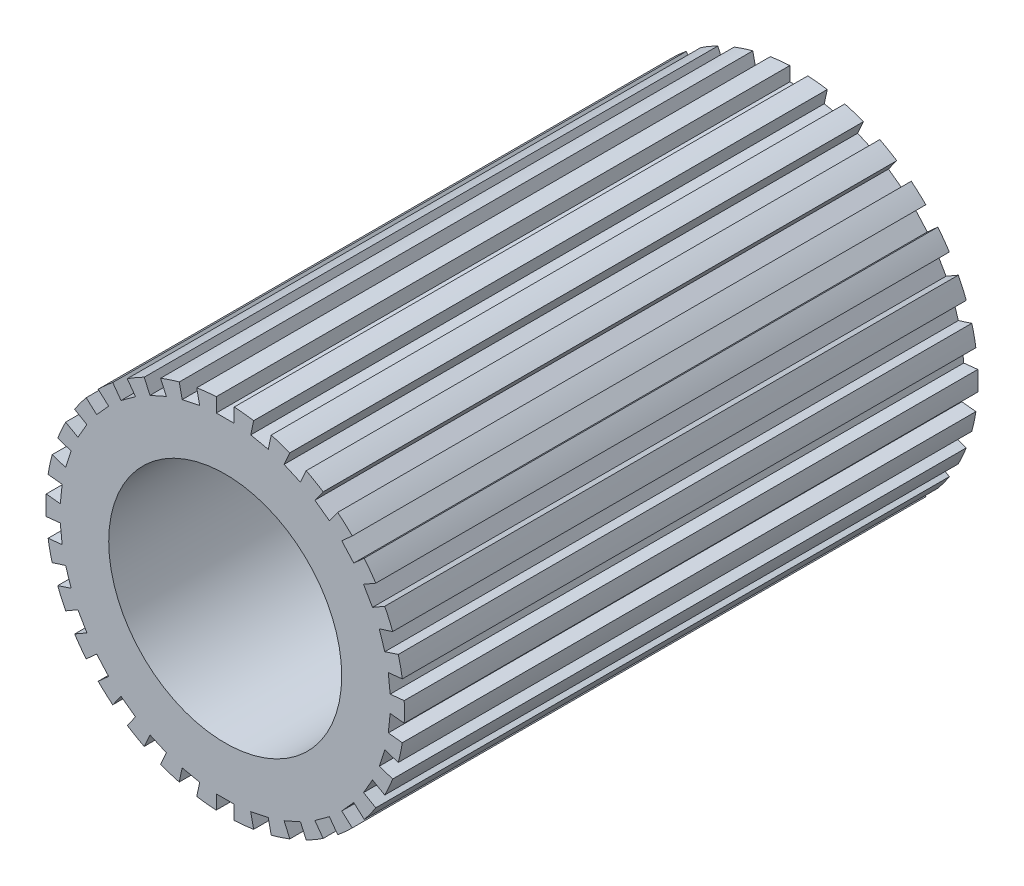
SolidWorks part; units mm, degrees
material "ABS"
ref_plane "Front Plane" through (0, 0, 0) normal (0, 0, 1) x (1, 0, 0)
ref_plane "Top Plane" through (0, 0, 0) normal (0, 1, 0) x (1, 0, 0)
ref_plane "Right Plane" through (0, 0, 0) normal (1, 0, 0) x (0, 0, -1)
sketch "Sketch1" plane through (0, 0, 0) normal (0, 0, 1) x (1, 0, 0)
  circle A0 centre (0, 0) radius 2.5
  circle A1 centre (0, 0) radius 1.625
  dimension "D1" = 3.25
  dimension "D2" = 5
extrude "Boss-Extrude1" add sketch "Sketch1" along normal blind 4
extrude "Boss-Extrude2" add sketch "Sketch1<2>" against normal blind 4 contours A1 | A0 A1 region at (-2.4293, 0, 0) region at (0, 0, 0)
sketch "Sketch1<2>" plane through (0, 0, 0) normal (0, 0, 1) x (1, 0, 0) same geometry as "Sketch1"
sketch "Sketch2" plane through (0, 0, 4) normal (0, 0, 1) x (1, 0, 0)
  line L0 (0.3559, 2.2757) -> (0.5638, 3.2539)
  line L1 (-0.125, 2.3) -> (0.125, 2.3)
  line L2 (-0.125, 2.3) -> (-0.125, 3.3)
  line L3 (-0.125, 3.3) -> (0.125, 3.3)
  line L4 (0.125, 2.3) -> (0.125, 3.3)
  line L5 (0.3559, 2.2757) -> (0.6005, 2.2238)
  line L6 (0.6005, 2.2238) -> (0.8084, 3.2019)
  line L7 (0.5638, 3.2539) -> (0.8084, 3.2019)
  line L8 (0.8213, 2.152) -> (1.228, 3.0655)
  line L9 (0.8213, 2.152) -> (1.0497, 2.0503)
  line L10 (1.0497, 2.0503) -> (1.4564, 2.9639)
  line L11 (1.228, 3.0655) -> (1.4564, 2.9639)
  line L12 (1.2508, 1.9342) -> (1.8386, 2.7432)
  line L13 (1.2508, 1.9342) -> (1.453, 1.7873)
  line L14 (1.453, 1.7873) -> (2.0408, 2.5963)
  line L15 (1.8386, 2.7432) -> (2.0408, 2.5963)
  line L16 (1.6256, 1.6319) -> (2.3687, 2.301)
  line L17 (1.6256, 1.6319) -> (1.7929, 1.4461)
  line L18 (1.7929, 1.4461) -> (2.536, 2.1152)
  line L19 (2.3687, 2.301) -> (2.536, 2.1152)
  line L20 (1.9294, 1.2583) -> (2.7954, 1.7583)
  line L21 (1.9294, 1.2583) -> (2.0544, 1.0417)
  line L22 (2.0544, 1.0417) -> (2.9204, 1.5417)
  line L23 (2.7954, 1.7583) -> (2.9204, 1.5417)
  line L24 (2.1488, 0.8296) -> (3.0999, 1.1386)
  line L25 (2.1488, 0.8296) -> (2.2261, 0.5919)
  line L26 (2.2261, 0.5919) -> (3.1771, 0.9009)
  line L27 (3.0999, 1.1386) -> (3.1771, 0.9009)
  line L28 (2.2743, 0.3647) -> (3.2689, 0.4693)
  line L29 (2.2743, 0.3647) -> (2.3005, 0.1161)
  line L30 (2.3005, 0.1161) -> (3.295, 0.2206)
  line L31 (3.2689, 0.4693) -> (3.295, 0.2206)
  line L32 (2.3005, -0.1161) -> (3.295, -0.2206)
  line L33 (2.3005, -0.1161) -> (2.2743, -0.3647)
  line L34 (2.2743, -0.3647) -> (3.2689, -0.4693)
  line L35 (3.295, -0.2206) -> (3.2689, -0.4693)
  line L36 (2.2261, -0.5919) -> (3.1771, -0.9009)
  line L37 (2.2261, -0.5919) -> (2.1488, -0.8296)
  line L38 (2.1488, -0.8296) -> (3.0999, -1.1386)
  line L39 (3.1771, -0.9009) -> (3.0999, -1.1386)
  line L40 (2.0544, -1.0417) -> (2.9204, -1.5417)
  line L41 (2.0544, -1.0417) -> (1.9294, -1.2583)
  line L42 (1.9294, -1.2583) -> (2.7954, -1.7583)
  line L43 (2.9204, -1.5417) -> (2.7954, -1.7583)
  line L44 (1.7929, -1.4461) -> (2.536, -2.1152)
  line L45 (1.7929, -1.4461) -> (1.6256, -1.6319)
  line L46 (1.6256, -1.6319) -> (2.3687, -2.301)
  line L47 (2.536, -2.1152) -> (2.3687, -2.301)
  line L48 (1.453, -1.7873) -> (2.0408, -2.5963)
  line L49 (1.453, -1.7873) -> (1.2508, -1.9342)
  line L50 (1.2508, -1.9342) -> (1.8386, -2.7432)
  line L51 (2.0408, -2.5963) -> (1.8386, -2.7432)
  line L52 (1.0497, -2.0503) -> (1.4564, -2.9639)
  line L53 (1.0497, -2.0503) -> (0.8213, -2.152)
  line L54 (0.8213, -2.152) -> (1.228, -3.0655)
  line L55 (1.4564, -2.9639) -> (1.228, -3.0655)
  line L56 (0.6005, -2.2238) -> (0.8084, -3.2019)
  line L57 (0.6005, -2.2238) -> (0.3559, -2.2757)
  line L58 (0.3559, -2.2757) -> (0.5638, -3.2539)
  line L59 (0.8084, -3.2019) -> (0.5638, -3.2539)
  line L60 (0.125, -2.3) -> (0.125, -3.3)
  line L61 (0.125, -2.3) -> (-0.125, -2.3)
  line L62 (-0.125, -2.3) -> (-0.125, -3.3)
  line L63 (0.125, -3.3) -> (-0.125, -3.3)
  line L64 (-0.3559, -2.2757) -> (-0.5638, -3.2539)
  line L65 (-0.3559, -2.2757) -> (-0.6005, -2.2238)
  line L66 (-0.6005, -2.2238) -> (-0.8084, -3.2019)
  line L67 (-0.5638, -3.2539) -> (-0.8084, -3.2019)
  line L68 (-0.8213, -2.152) -> (-1.228, -3.0655)
  line L69 (-0.8213, -2.152) -> (-1.0497, -2.0503)
  line L70 (-1.0497, -2.0503) -> (-1.4564, -2.9639)
  line L71 (-1.228, -3.0655) -> (-1.4564, -2.9639)
  line L72 (-1.2508, -1.9342) -> (-1.8386, -2.7432)
  line L73 (-1.2508, -1.9342) -> (-1.453, -1.7873)
  line L74 (-1.453, -1.7873) -> (-2.0408, -2.5963)
  line L75 (-1.8386, -2.7432) -> (-2.0408, -2.5963)
  line L76 (-1.6256, -1.6319) -> (-2.3687, -2.301)
  line L77 (-1.6256, -1.6319) -> (-1.7929, -1.4461)
  line L78 (-1.7929, -1.4461) -> (-2.536, -2.1152)
  line L79 (-2.3687, -2.301) -> (-2.536, -2.1152)
  line L80 (-1.9294, -1.2583) -> (-2.7954, -1.7583)
  line L81 (-1.9294, -1.2583) -> (-2.0544, -1.0417)
  line L82 (-2.0544, -1.0417) -> (-2.9204, -1.5417)
  line L83 (-2.7954, -1.7583) -> (-2.9204, -1.5417)
  line L84 (-2.1488, -0.8296) -> (-3.0999, -1.1386)
  line L85 (-2.1488, -0.8296) -> (-2.2261, -0.5919)
  line L86 (-2.2261, -0.5919) -> (-3.1771, -0.9009)
  line L87 (-3.0999, -1.1386) -> (-3.1771, -0.9009)
  line L88 (-2.2743, -0.3647) -> (-3.2689, -0.4693)
  line L89 (-2.2743, -0.3647) -> (-2.3005, -0.1161)
  line L90 (-2.3005, -0.1161) -> (-3.295, -0.2206)
  line L91 (-3.2689, -0.4693) -> (-3.295, -0.2206)
  line L92 (-2.3005, 0.1161) -> (-3.295, 0.2206)
  line L93 (-2.3005, 0.1161) -> (-2.2743, 0.3647)
  line L94 (-2.2743, 0.3647) -> (-3.2689, 0.4693)
  line L95 (-3.295, 0.2206) -> (-3.2689, 0.4693)
  line L96 (-2.2261, 0.5919) -> (-3.1771, 0.9009)
  line L97 (-2.2261, 0.5919) -> (-2.1488, 0.8296)
  line L98 (-2.1488, 0.8296) -> (-3.0999, 1.1386)
  line L99 (-3.1771, 0.9009) -> (-3.0999, 1.1386)
  line L100 (-2.0544, 1.0417) -> (-2.9204, 1.5417)
  line L101 (-2.0544, 1.0417) -> (-1.9294, 1.2583)
  line L102 (-1.9294, 1.2583) -> (-2.7954, 1.7583)
  line L103 (-2.9204, 1.5417) -> (-2.7954, 1.7583)
  line L104 (-1.7929, 1.4461) -> (-2.536, 2.1152)
  line L105 (-1.7929, 1.4461) -> (-1.6256, 1.6319)
  line L106 (-1.6256, 1.6319) -> (-2.3687, 2.301)
  line L107 (-2.536, 2.1152) -> (-2.3687, 2.301)
  line L108 (-1.453, 1.7873) -> (-2.0408, 2.5963)
  line L109 (-1.453, 1.7873) -> (-1.2508, 1.9342)
  line L110 (-1.2508, 1.9342) -> (-1.8386, 2.7432)
  line L111 (-2.0408, 2.5963) -> (-1.8386, 2.7432)
  line L112 (-1.0497, 2.0503) -> (-1.4564, 2.9639)
  line L113 (-1.0497, 2.0503) -> (-0.8213, 2.152)
  line L114 (-0.8213, 2.152) -> (-1.228, 3.0655)
  line L115 (-1.4564, 2.9639) -> (-1.228, 3.0655)
  line L116 (-0.6005, 2.2238) -> (-0.8084, 3.2019)
  line L117 (-0.6005, 2.2238) -> (-0.3559, 2.2757)
  line L118 (-0.3559, 2.2757) -> (-0.5638, 3.2539)
  line L119 (-0.8084, 3.2019) -> (-0.5638, 3.2539)
  point P4 (0, 3.3)
  point P124 (0, 0)
  dimension "D1" = 0.25
  dimension "D2" = 1
  dimension "D3" = 2.3
  dimension "D4" = 30
extrude "Cut-Extrude1" cut sketch "Sketch2" against normal through all
